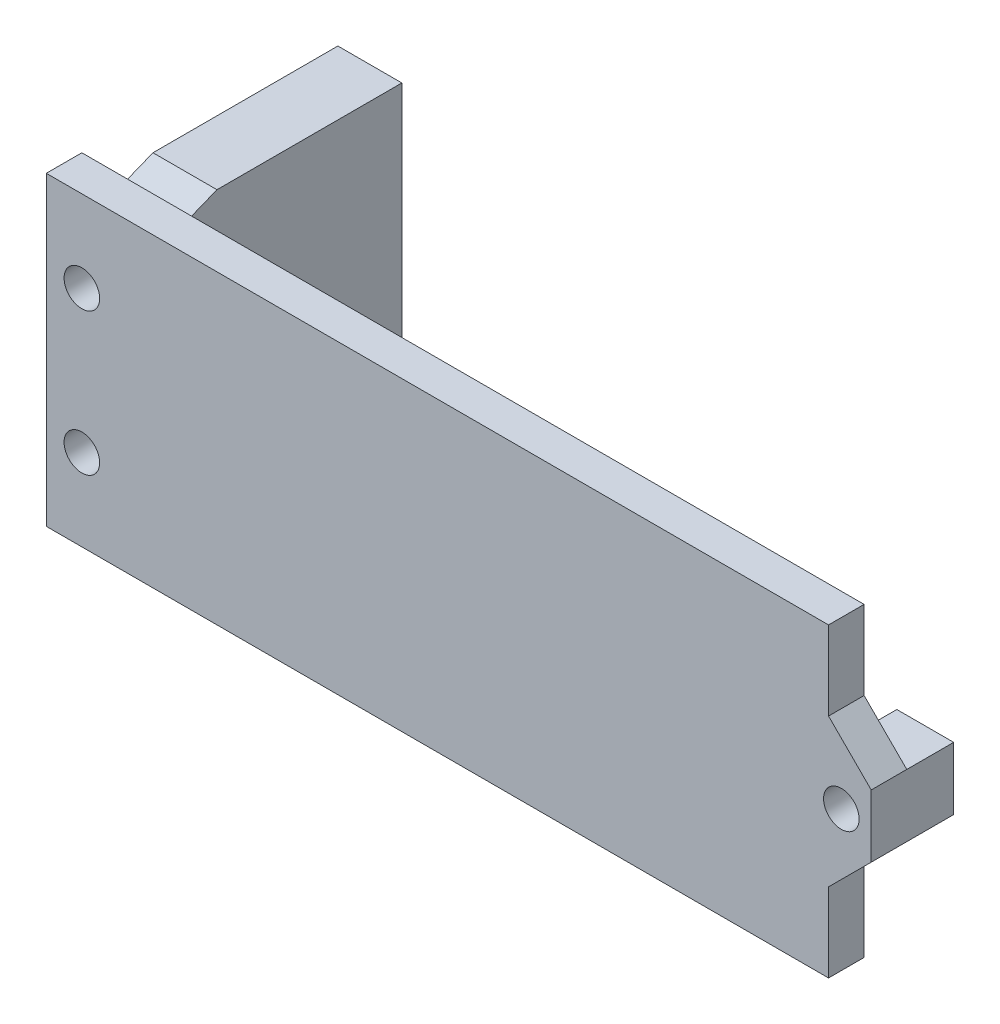
SolidWorks part; units mm, degrees
ref_plane "Front Plane" through (0, 0, 0) normal (0, 0, 1) x (1, 0, 0)
ref_plane "Top Plane" through (0, 0, 0) normal (0, 1, 0) x (1, 0, 0)
ref_plane "Right Plane" through (0, 0, 0) normal (1, 0, 0) x (0, 0, -1)
sketch "Sketch1" plane through (0, 0, 0) normal (0, 0, 1) x (1, 0, 0)
  line L0 (-64.135, 20.955) -> (-64.135, 0)
  line L1 (0, 0) -> (-69.85, 0)
  line L2 (0, 0) -> (0, 20.955)
  line L3 (0, 20.955) -> (-69.85, 20.955)
  line L4 (-69.85, 0) -> (-69.85, 20.955)
  line L6 (0, 13.2715) -> (3.81, 13.2715)
  line L7 (0, 13.2715) -> (0, 7.6835)
  line L8 (0, 7.6835) -> (3.81, 7.6835)
  line L9 (3.81, 13.2715) -> (3.81, 7.6835)
  line L10 (0, 13.2715) -> (-1.27, 13.2715)
  line L11 (0, 13.2715) -> (0, 7.6835)
  line L12 (0, 7.6835) -> (-1.27, 7.6835)
  line L13 (-1.27, 13.2715) -> (-1.27, 7.6835)
  circle A0 centre (-66.675, 16.8275) radius 1.5875
  circle A1 centre (-66.675, 4.1275) radius 1.5875
  circle A2 centre (1.143, 10.4775) radius 1.5875
  point P11 (0, 10.4775)
  point P16 (3.81, 10.4775)
  dimension "D1" = 3.175
  dimension "D10" = 3.175
  dimension "D2" = 69.85
  dimension "D3" = 3.175
  dimension "D4" = 4.1275
  dimension "D5" = 20.955
  dimension "D6" = 5.715
  dimension "D7" = 4.1275
  dimension "D8" = 5.588
  dimension "D9" = 3.81
  dimension "D11" = 1.143
  dimension "D12" = 1.27
extrude "Boss-Extrude1" add sketch "Sketch1" along normal blind 3.175 contours L2 L3 L0 L1 | L4 L1 L0 L3 A0 | L9 L6 L2 L8 A2 | A2 L2 L10 L13 L12 region at (-32.2344, 10.4775, 0) region at (-67.0409, 10.4775, 0) region at (1.905, 13.2039, 0) region at (-0.6827, 10.4775, 0)
extrude "Boss-Extrude2" add sketch "Sketch1<3>" against normal blind 22.86 contours L4 L1 L0 L3 A0 region at (-67.0409, 10.4775, 0)
sketch "Sketch1<3>" plane through (0, 0, 0) normal (0, 0, 1) x (1, 0, 0) same geometry as "Sketch1"
extrude "Boss-Extrude3" add sketch "Sketch1<4>" against normal blind 4.191 contours L9 L6 L2 L8 A2 | A2 L2 L10 L13 L12 region at (1.905, 13.2039, 0) region at (-0.6827, 10.4775, 0)
sketch "Sketch1<4>" plane through (0, 0, 0) normal (0, 0, 1) x (1, 0, 0) same geometry as "Sketch1"
chamfer "Chamfer1" distance 3.81 angle 45 2 edges at (0, 13.2715, 1.5875) (0, 7.6835, 1.5875)
sketch "Sketch3" plane through (0, 20.955, 0) normal (0, 1, 0) x (1, 0, 0)
  line L1 (-69.85, -3.175) -> (0, -3.175)
  line L2 (-69.85, -3.175) -> (-69.85, 0)
  line L3 (-69.85, 0) -> (0, 0)
  line L4 (0, -3.175) -> (0, 0)
extrude "Boss-Extrude4" add sketch "Sketch3" along normal blind 3.175
ref_plane "Plane1" through (0, 10.4775, 0) normal (0, -1, 0) x (-1, 0, 0)
mirror "Mirror1" about plane through (0, 10.4775, 0) normal (0, -1, 0) of "Boss-Extrude4"
sketch "Sketch6" plane through (-64.135, 0, 0) normal (1, 0, 0) x (0, 0, -1)
  line L0 (0, 20.955) -> (3.175, 19.685)
  line L1 (3.175, 19.685) -> (6.35, 20.955)
  line L2 (22.86, 20.955) -> (0, 20.955) construction
  line L3 (6.35, 20.955) -> (0, 20.955)
  line L4 (-3.1433, 10.4775) -> (3.1433, 10.4775) construction
  line L5 (3.175, 1.27) -> (6.35, 0)
  line L6 (0, 0) -> (3.175, 1.27)
  line L7 (6.35, 0) -> (0, 0)
  point P3 (3.799, 17.8419)
  point P12 (3.0301, 17.7833)
  point P13 (3.175, 20.955)
  point P14 (3.175, 17.78)
  dimension "D1" = 6.35
  dimension "D2" = 1.27
extrude "Cut-Extrude6" cut sketch "Sketch6" against normal through all
